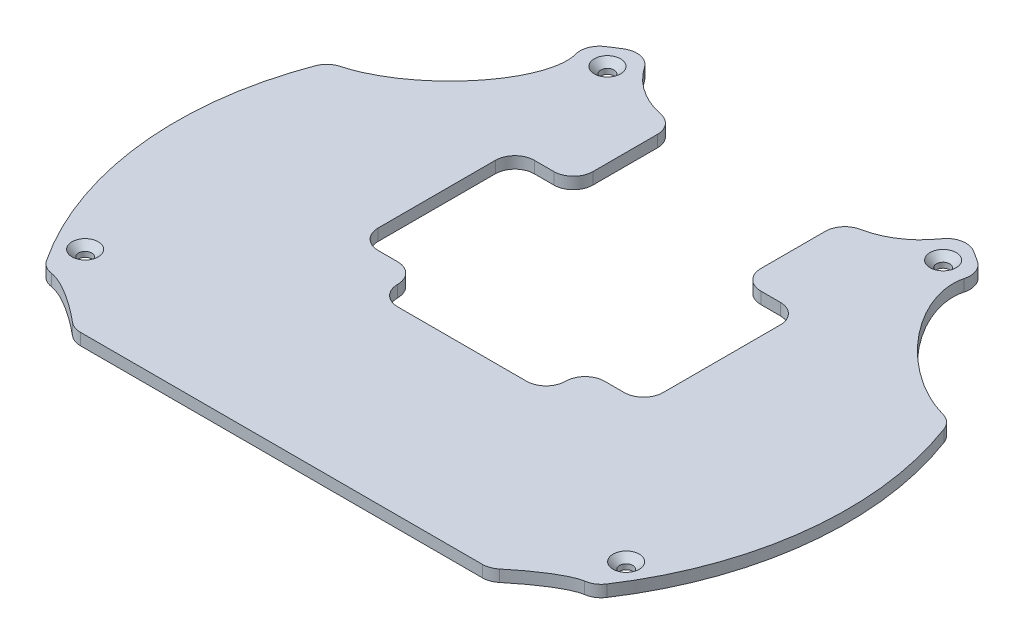
SolidWorks part; units mm, degrees
ref_plane "Plano frontal" through (0, 0, 0) normal (0, 0, 1) x (1, 0, 0)
ref_plane "Plano superior" through (0, 0, 0) normal (0, 1, 0) x (1, 0, 0)
ref_plane "Plano direito" through (0, 0, 0) normal (1, 0, 0) x (0, 0, -1)
sketch "Esboço3" plane through (0, 0, 0) normal (0, 1, 0) x (1, 0, 0)
  line L0 (-21.5, 63.2691) -> (-21.5, 37.2691)
  line L1 (-21.5, -12.7309) -> (21.5, -12.7309)
  line L2 (21.5, 63.2691) -> (21.5, 37.2691)
  line L3 (0, 0) -> (0, -78.0563) construction
  line L6 (0, 0) -> (-139.4559, 0) construction
  line L12 (-53.2866, -59) -> (53.2866, -59)
  line L13 (-21.5, -2.7309) -> (-36.5, -2.7309)
  line L14 (-36.5, -2.7309) -> (-36.5, 37.2691)
  line L15 (-36.5, 37.2691) -> (-21.5, 37.2691)
  line L16 (21.5, -2.7309) -> (36.5, -2.7309)
  line L17 (36.5, -2.7309) -> (36.5, 37.2691)
  line L18 (36.5, 37.2691) -> (21.5, 37.2691)
  line L19 (-21.5, -2.7309) -> (-21.5, -12.7309)
  line L20 (21.5, -2.7309) -> (21.5, -12.7309)
  arc A0 (-40.1522, 76.0513) -> (-51.3328, 68.9996) centre (0, 0) ccw
  arc A2 (-79.5093, 32.776) -> (-69.9714, -50) centre (0, 0) ccw
  arc A4 (69.9714, -50) -> (79.5093, 32.776) centre (0, 0) ccw
  arc A5 (51.3328, 68.9996) -> (40.1522, 76.0513) centre (0, 0) ccw
  arc A6 (-21.5, 63.2691) -> (-40.1522, 76.0513) centre (-21.5, 83.2691) cw
  arc A7 (21.5, 63.2691) -> (40.1522, 76.0513) centre (21.5, 83.2691) ccw
  ellipse E0 centre (-53.184, -65.8196) end of major axis (-36.3967, -81.6392) minor radius 5 (-53.2866, -59) -> (-69.9714, -50) ccw
  ellipse E1 centre (53.184, -65.8196) end of major axis (36.3967, -81.6392) minor radius 5 (53.2866, -59) -> (69.9714, -50) cw
  ellipse E2 centre (-69.6217, 51.955) end of major axis (-87.9105, 34.9104) minor radius 12.5 (-79.5093, 32.776) -> (-51.3328, 68.9996) ccw
  ellipse E3 centre (69.6217, 51.955) end of major axis (51.3328, 68.9996) minor radius 12.5 (79.5093, 32.776) -> (51.3328, 68.9996) cw
  point P8 (0, -12.7309)
  point P12 (0, -78.0563)
  point P21 (-60.4773, -60.4773)
  point P22 (-60.4773, 60.4773)
  dimension "D1" = 172
  dimension "D6" = 20
  dimension "D2" = 96
  dimension "D3" = 21.5
  dimension "D4" = 40
  dimension "D5" = 50
  dimension "D9" = 5
  dimension "D10" = 21.5
  dimension "D11" = 83.2691
  dimension "D12" = 59
  dimension "D13" = 15
  dimension "D14" = 10
  dimension "D15" = 50
  dimension "D16" = 25
extrude "Ressalto-extrusão2" add sketch "Esboço3" along normal blind 3
hole_wizard "Escareado para SFHCS M31" positions "Esboço11" profile "Esboço12" countersink size "M3" standard "Ansi Metric" end condition through all
sketch "Esboço11" plane through (0, 3, 0) normal (0, 1, 0) x (1, 0, 0)
  line L0 (0, 0) -> (0, 105.2199) construction
  line L2 (42.984, 67.4713) -> (0, 0) construction
  line L3 (0, 0) -> (69.282, -40) construction
  point P0 (42.984, 67.4713)
  point P2 (69.282, -40)
  point P19 (-69.282, -40)
  point P20 (-42.984, 67.4713)
  dimension "D1" = 32.5
  dimension "D2" = 60
  dimension "D3" = 80
  dimension "D4" = 80
sketch "Esboço12" plane through (42.984, 3, -67.4713) normal (1, 0, 0) x (0, 0, 1)
  line L0 (0, 0) -> (0, 3)
  line L1 (0, 3) -> (1.7, 3)
  line L2 (1.7, 3) -> (1.7, 1.66)
  line L3 (1.7, 1.66) -> (3.36, 0)
  line L5 (3.36, 0) -> (0, 0)
  line L6 (-1.7, 1.66) -> (-3.36, 0) construction
  line L11 (0, -6.35) -> (0, 107.95) construction
  dimension "Thru Hole Dia." = 3.4
  dimension "Thru Hole Depth" = 3
  dimension "Near C'Sink Dia." = 6.72
  dimension "Near C'Sink Angle" = 90
fillet "Filete4" radius 5 4 edges at (40.1522, 1.5, -76.0513) (21.5, 1.5, -63.2691) (-21.5, 1.5, -63.2691) (-40.1522, 1.5, -76.0513)
fillet "Filete6" radius 5 4 edges at (69.9714, 1.5, 50) (53.2866, 1.5, 59) (-53.2866, 1.5, 59) (-69.9714, 1.5, 50)
fillet "Filete7" radius 5 10 edges at (-21.5, 1.5, -37.2691) (-36.5, 1.5, -37.2691) (-36.5, 1.5, 2.7309) (-21.5, 1.5, 2.7309) (-21.5, 1.5, 12.7309) (21.5, 1.5, 12.7309) (21.5, 1.5, 2.7309) (36.5, 1.5, 2.7309) (36.5, 1.5, -37.2691) (21.5, 1.5, -37.2691)
fillet "Filete8" radius 5 4 edges at (79.5093, 1.5, -32.776) (51.3328, 1.5, -68.9996) (-79.5093, 1.5, -32.776) (-51.3328, 1.5, -68.9996)
